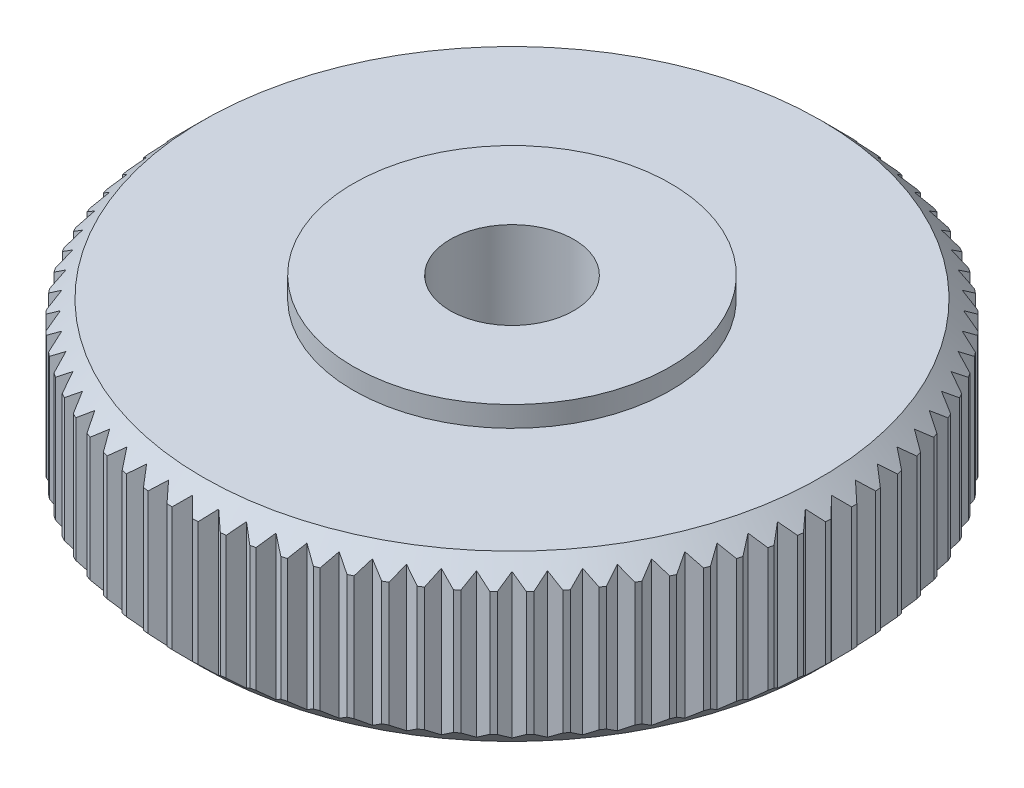
SolidWorks part; units mm, degrees
material "Chromowa stal nierdzewna"
ref_plane "Płaszczyzna przednia" through (0, 0, 0) normal (0, 0, 1) x (1, 0, 0)
ref_plane "Płaszczyzna górna" through (0, 0, 0) normal (0, 1, 0) x (1, 0, 0)
ref_plane "Płaszczyzna prawa" through (0, 0, 0) normal (1, 0, 0) x (0, 0, -1)
sketch "Szkic1" plane through (0, 0, 0) normal (0, 1, 0) x (1, 0, 0)
  circle A0 centre (0, 0) radius 8
  circle A1 centre (0, 0) radius 1.5
extrude "Dodanie-wyciągnięcie1" add sketch "Szkic1" along normal blind 4
chamfer "Sfazowanie1" distance 0.5 angle 45 2 edges at (0, 0, 8) (0, 4, 8)
sketch "Szkic2" plane through (0, 4, 0) normal (0, 1, 0) x (1, 0, 0)
  circle A0 centre (0, 0) radius 3.85
  circle A1 centre (0, 0) radius 1.5 construction
  circle A2 centre (0, 0) radius 1.5
extrude "Dodanie-wyciągnięcie2" add sketch "Szkic2" along normal blind 0.5
extrude "Dodanie-wyciągnięcie3" add sketch "Szkic2<2>" against normal blind 0.5 from surface starting at face at (0, 0, 7.5)
sketch "Szkic2<2>" plane through (0, 4, 0) normal (0, 1, 0) x (1, 0, 0) same geometry as "Szkic2"
sketch "Szkic3" plane through (0, 4, 0) normal (0, 1, 0) x (1, 0, 0)
  line L0 (8, 0) -> (7.75, 0) construction
  line L1 (7.996, -0.2524) -> (7.75, 0)
  line L2 (7.75, 0) -> (7.9962, 0.2476)
  line L3 (7.996, -0.2524) -> (8.6523, -0.2524)
  line L4 (8.6523, -0.2524) -> (8.6523, 0.2476)
  line L5 (7.9962, 0.2476) -> (8.6523, 0.2476)
  line L6 (7.9516, -0.8789) -> (7.7261, -0.6081)
  line L7 (7.7261, -0.6081) -> (7.9909, -0.3805)
  line L8 (7.9516, -0.8789) -> (8.6058, -0.9304)
  line L9 (8.6058, -0.9304) -> (8.645, -0.432)
  line L10 (7.9909, -0.3805) -> (8.645, -0.432)
  line L11 (7.9753, -0.6277) -> (7.7261, -0.6081) construction
  line L12 (7.8581, -1.5001) -> (7.6546, -1.2124)
  line L13 (7.6546, -1.2124) -> (7.9365, -1.0063)
  line L14 (7.8581, -1.5001) -> (8.5063, -1.6028)
  line L15 (8.5063, -1.6028) -> (8.5845, -1.1089)
  line L16 (7.9365, -1.0063) -> (8.5845, -1.1089)
  line L17 (7.9015, -1.2515) -> (7.6546, -1.2124) construction
  line L18 (7.7162, -2.112) -> (7.5359, -1.8092)
  line L19 (7.5359, -1.8092) -> (7.833, -1.6259)
  line L20 (7.7162, -2.112) -> (8.3543, -2.2652)
  line L21 (8.3543, -2.2652) -> (8.471, -1.779)
  line L22 (7.833, -1.6259) -> (8.471, -1.779)
  line L23 (7.779, -1.8676) -> (7.5359, -1.8092) construction
  line L24 (7.5267, -2.7109) -> (7.3707, -2.3949)
  line L25 (7.3707, -2.3949) -> (7.6813, -2.2354)
  line L26 (7.5267, -2.7109) -> (8.1508, -2.9137)
  line L27 (8.1508, -2.9137) -> (8.3053, -2.4382)
  line L28 (7.6813, -2.2354) -> (8.3053, -2.4382)
  line L29 (7.6085, -2.4721) -> (7.3707, -2.3949) construction
  line L30 (7.2908, -3.2931) -> (7.1601, -2.9658)
  line L31 (7.1601, -2.9658) -> (7.4823, -2.8312)
  line L32 (7.2908, -3.2931) -> (7.8971, -3.5442)
  line L33 (7.8971, -3.5442) -> (8.0884, -3.0823)
  line L34 (7.4823, -2.8312) -> (8.0884, -3.0823)
  line L35 (7.391, -3.0615) -> (7.1601, -2.9658) construction
  line L36 (7.0099, -3.855) -> (6.9053, -3.5184)
  line L37 (6.9053, -3.5184) -> (7.2371, -3.4095)
  line L38 (7.0099, -3.855) -> (7.5947, -4.1529)
  line L39 (7.5947, -4.1529) -> (7.8217, -3.7074)
  line L40 (7.2371, -3.4095) -> (7.8217, -3.7074)
  line L41 (7.1281, -3.6319) -> (6.9053, -3.5184) construction
  line L42 (6.6859, -4.3931) -> (6.608, -4.0494)
  line L43 (6.608, -4.0494) -> (6.9472, -3.9668)
  line L44 (6.6859, -4.3931) -> (7.2454, -4.736)
  line L45 (7.2454, -4.736) -> (7.5067, -4.3096)
  line L46 (6.9472, -3.9668) -> (7.5067, -4.3096)
  line L47 (6.8211, -4.18) -> (6.608, -4.0494) construction
  line L48 (6.3206, -4.9041) -> (6.2699, -4.5553)
  line L49 (6.2699, -4.5553) -> (6.6146, -4.4997)
  line L50 (6.3206, -4.9041) -> (6.8515, -5.2898)
  line L51 (6.8515, -5.2898) -> (7.1454, -4.8853)
  line L52 (6.6146, -4.4997) -> (7.1454, -4.8853)
  line L53 (6.4721, -4.7023) -> (6.2699, -4.5553) construction
  line L54 (5.9163, -5.3849) -> (5.8931, -5.0332)
  line L55 (5.8931, -5.0332) -> (6.2412, -5.0048)
  line L56 (5.9163, -5.3849) -> (6.4153, -5.8111)
  line L57 (6.4153, -5.8111) -> (6.7401, -5.4309)
  line L58 (6.2412, -5.0048) -> (6.7401, -5.4309)
  line L59 (6.0832, -5.1956) -> (5.8931, -5.0332) construction
  line L60 (5.4756, -5.8325) -> (5.4801, -5.4801)
  line L61 (5.4801, -5.4801) -> (5.8293, -5.479)
  line L62 (5.4756, -5.8325) -> (5.9396, -6.2965)
  line L63 (5.9396, -6.2965) -> (6.2932, -5.943)
  line L64 (5.8293, -5.479) -> (6.2932, -5.943)
  line L65 (5.6569, -5.6569) -> (5.4801, -5.4801) construction
  line L66 (5.0011, -6.2441) -> (5.0332, -5.8931)
  line L67 (5.0332, -5.8931) -> (5.3814, -5.9195)
  line L68 (5.0011, -6.2441) -> (5.4273, -6.7431)
  line L69 (5.4273, -6.7431) -> (5.8075, -6.4184)
  line L70 (5.3814, -5.9195) -> (5.8075, -6.4184)
  line L71 (5.1956, -6.0832) -> (5.0332, -5.8931) construction
  line L72 (4.4958, -6.6172) -> (4.5553, -6.2699)
  line L73 (4.5553, -6.2699) -> (4.9004, -6.3235)
  line L74 (4.4958, -6.6172) -> (4.8815, -7.1482)
  line L75 (4.8815, -7.1482) -> (5.286, -6.8543)
  line L76 (4.9004, -6.3235) -> (5.286, -6.8543)
  line L77 (4.7023, -6.4721) -> (4.5553, -6.2699) construction
  line L78 (3.9627, -6.9496) -> (4.0494, -6.608)
  line L79 (4.0494, -6.608) -> (4.3891, -6.6885)
  line L80 (3.9627, -6.9496) -> (4.3056, -7.5091)
  line L81 (4.3056, -7.5091) -> (4.732, -7.2479)
  line L82 (4.3891, -6.6885) -> (4.732, -7.2479)
  line L83 (4.18, -6.8211) -> (4.0494, -6.608) construction
  line L84 (3.4053, -7.2391) -> (3.5184, -6.9053)
  line L85 (3.5184, -6.9053) -> (3.8508, -7.0122)
  line L86 (3.4053, -7.2391) -> (3.7032, -7.8238)
  line L87 (3.7032, -7.8238) -> (4.1487, -7.5968)
  line L88 (3.8508, -7.0122) -> (4.1487, -7.5968)
  line L89 (3.6319, -7.1281) -> (3.5184, -6.9053) construction
  line L90 (2.8268, -7.4839) -> (2.9658, -7.1601)
  line L91 (2.9658, -7.1601) -> (3.2888, -7.2927)
  line L92 (2.8268, -7.4839) -> (3.0779, -8.0902)
  line L93 (3.0779, -8.0902) -> (3.5399, -7.8989)
  line L94 (3.2888, -7.2927) -> (3.5399, -7.8989)
  line L95 (3.0615, -7.391) -> (2.9658, -7.1601) construction
  line L96 (2.2309, -7.6826) -> (2.3949, -7.3707)
  line L97 (2.3949, -7.3707) -> (2.7065, -7.5283)
  line L98 (2.2309, -7.6826) -> (2.4337, -8.3068)
  line L99 (2.4337, -8.3068) -> (2.9092, -8.1523)
  line L100 (2.7065, -7.5283) -> (2.9092, -8.1523)
  line L101 (2.4721, -7.6085) -> (2.3949, -7.3707) construction
  line L102 (1.6213, -7.834) -> (1.8092, -7.5359)
  line L103 (1.8092, -7.5359) -> (2.1075, -7.7174)
  line L104 (1.6213, -7.834) -> (1.7745, -8.4721)
  line L105 (1.7745, -8.4721) -> (2.2606, -8.3554)
  line L106 (2.1075, -7.7174) -> (2.2606, -8.3554)
  line L107 (1.8676, -7.779) -> (1.8092, -7.5359) construction
  line L108 (1.0016, -7.9371) -> (1.2124, -7.6546)
  line L109 (1.2124, -7.6546) -> (1.4955, -7.859)
  line L110 (1.0016, -7.9371) -> (1.1043, -8.5852)
  line L111 (1.1043, -8.5852) -> (1.5981, -8.507)
  line L112 (1.4955, -7.859) -> (1.5981, -8.507)
  line L113 (1.2515, -7.9015) -> (1.2124, -7.6546) construction
  line L114 (0.3758, -7.9912) -> (0.6081, -7.7261)
  line L115 (0.6081, -7.7261) -> (0.8743, -7.9521)
  line L116 (0.3758, -7.9912) -> (0.4273, -8.6454)
  line L117 (0.4273, -8.6454) -> (0.9257, -8.6062)
  line L118 (0.8743, -7.9521) -> (0.9257, -8.6062)
  line L119 (0.6277, -7.9753) -> (0.6081, -7.7261) construction
  line L120 (-0.2524, -7.996) -> (0, -7.75)
  line L121 (0, -7.75) -> (0.2476, -7.9962)
  line L122 (-0.2524, -7.996) -> (-0.2524, -8.6523)
  line L123 (-0.2524, -8.6523) -> (0.2476, -8.6523)
  line L124 (0.2476, -7.9962) -> (0.2476, -8.6523)
  line L125 (0, -8) -> (0, -7.75) construction
  line L126 (-0.8789, -7.9516) -> (-0.6081, -7.7261)
  line L127 (-0.6081, -7.7261) -> (-0.3805, -7.9909)
  line L128 (-0.8789, -7.9516) -> (-0.9304, -8.6058)
  line L129 (-0.9304, -8.6058) -> (-0.432, -8.645)
  line L130 (-0.3805, -7.9909) -> (-0.432, -8.645)
  line L131 (-0.6277, -7.9753) -> (-0.6081, -7.7261) construction
  line L132 (-1.5001, -7.8581) -> (-1.2124, -7.6546)
  line L133 (-1.2124, -7.6546) -> (-1.0063, -7.9365)
  line L134 (-1.5001, -7.8581) -> (-1.6028, -8.5063)
  line L135 (-1.6028, -8.5063) -> (-1.1089, -8.5845)
  line L136 (-1.0063, -7.9365) -> (-1.1089, -8.5845)
  line L137 (-1.2515, -7.9015) -> (-1.2124, -7.6546) construction
  line L138 (-2.112, -7.7162) -> (-1.8092, -7.5359)
  line L139 (-1.8092, -7.5359) -> (-1.6259, -7.833)
  line L140 (-2.112, -7.7162) -> (-2.2652, -8.3543)
  line L141 (-2.2652, -8.3543) -> (-1.779, -8.471)
  line L142 (-1.6259, -7.833) -> (-1.779, -8.471)
  line L143 (-1.8676, -7.779) -> (-1.8092, -7.5359) construction
  line L144 (-2.7109, -7.5267) -> (-2.3949, -7.3707)
  line L145 (-2.3949, -7.3707) -> (-2.2354, -7.6813)
  line L146 (-2.7109, -7.5267) -> (-2.9137, -8.1508)
  line L147 (-2.9137, -8.1508) -> (-2.4382, -8.3053)
  line L148 (-2.2354, -7.6813) -> (-2.4382, -8.3053)
  line L149 (-2.4721, -7.6085) -> (-2.3949, -7.3707) construction
  line L150 (-3.2931, -7.2908) -> (-2.9658, -7.1601)
  line L151 (-2.9658, -7.1601) -> (-2.8312, -7.4823)
  line L152 (-3.2931, -7.2908) -> (-3.5442, -7.8971)
  line L153 (-3.5442, -7.8971) -> (-3.0823, -8.0884)
  line L154 (-2.8312, -7.4823) -> (-3.0823, -8.0884)
  line L155 (-3.0615, -7.391) -> (-2.9658, -7.1601) construction
  line L156 (-3.855, -7.0099) -> (-3.5184, -6.9053)
  line L157 (-3.5184, -6.9053) -> (-3.4095, -7.2371)
  line L158 (-3.855, -7.0099) -> (-4.1529, -7.5947)
  line L159 (-4.1529, -7.5947) -> (-3.7074, -7.8217)
  line L160 (-3.4095, -7.2371) -> (-3.7074, -7.8217)
  line L161 (-3.6319, -7.1281) -> (-3.5184, -6.9053) construction
  line L162 (-4.3931, -6.6859) -> (-4.0494, -6.608)
  line L163 (-4.0494, -6.608) -> (-3.9668, -6.9472)
  line L164 (-4.3931, -6.6859) -> (-4.736, -7.2454)
  line L165 (-4.736, -7.2454) -> (-4.3096, -7.5067)
  line L166 (-3.9668, -6.9472) -> (-4.3096, -7.5067)
  line L167 (-4.18, -6.8211) -> (-4.0494, -6.608) construction
  line L168 (-4.9041, -6.3206) -> (-4.5553, -6.2699)
  line L169 (-4.5553, -6.2699) -> (-4.4997, -6.6146)
  line L170 (-4.9041, -6.3206) -> (-5.2898, -6.8515)
  line L171 (-5.2898, -6.8515) -> (-4.8853, -7.1454)
  line L172 (-4.4997, -6.6146) -> (-4.8853, -7.1454)
  line L173 (-4.7023, -6.4721) -> (-4.5553, -6.2699) construction
  line L174 (-5.3849, -5.9163) -> (-5.0332, -5.8931)
  line L175 (-5.0332, -5.8931) -> (-5.0048, -6.2412)
  line L176 (-5.3849, -5.9163) -> (-5.8111, -6.4153)
  line L177 (-5.8111, -6.4153) -> (-5.4309, -6.7401)
  line L178 (-5.0048, -6.2412) -> (-5.4309, -6.7401)
  line L179 (-5.1956, -6.0832) -> (-5.0332, -5.8931) construction
  line L180 (-5.8325, -5.4756) -> (-5.4801, -5.4801)
  line L181 (-5.4801, -5.4801) -> (-5.479, -5.8293)
  line L182 (-5.8325, -5.4756) -> (-6.2965, -5.9396)
  line L183 (-6.2965, -5.9396) -> (-5.943, -6.2932)
  line L184 (-5.479, -5.8293) -> (-5.943, -6.2932)
  line L185 (-5.6569, -5.6569) -> (-5.4801, -5.4801) construction
  line L186 (-6.2441, -5.0011) -> (-5.8931, -5.0332)
  line L187 (-5.8931, -5.0332) -> (-5.9195, -5.3814)
  line L188 (-6.2441, -5.0011) -> (-6.7431, -5.4273)
  line L189 (-6.7431, -5.4273) -> (-6.4184, -5.8075)
  line L190 (-5.9195, -5.3814) -> (-6.4184, -5.8075)
  line L191 (-6.0832, -5.1956) -> (-5.8931, -5.0332) construction
  line L192 (-6.6172, -4.4958) -> (-6.2699, -4.5553)
  line L193 (-6.2699, -4.5553) -> (-6.3235, -4.9004)
  line L194 (-6.6172, -4.4958) -> (-7.1482, -4.8815)
  line L195 (-7.1482, -4.8815) -> (-6.8543, -5.286)
  line L196 (-6.3235, -4.9004) -> (-6.8543, -5.286)
  line L197 (-6.4721, -4.7023) -> (-6.2699, -4.5553) construction
  line L198 (-6.9496, -3.9627) -> (-6.608, -4.0494)
  line L199 (-6.608, -4.0494) -> (-6.6885, -4.3891)
  line L200 (-6.9496, -3.9627) -> (-7.5091, -4.3056)
  line L201 (-7.5091, -4.3056) -> (-7.2479, -4.732)
  line L202 (-6.6885, -4.3891) -> (-7.2479, -4.732)
  line L203 (-6.8211, -4.18) -> (-6.608, -4.0494) construction
  line L204 (-7.2391, -3.4053) -> (-6.9053, -3.5184)
  line L205 (-6.9053, -3.5184) -> (-7.0122, -3.8508)
  line L206 (-7.2391, -3.4053) -> (-7.8238, -3.7032)
  line L207 (-7.8238, -3.7032) -> (-7.5968, -4.1487)
  line L208 (-7.0122, -3.8508) -> (-7.5968, -4.1487)
  line L209 (-7.1281, -3.6319) -> (-6.9053, -3.5184) construction
  line L210 (-7.4839, -2.8268) -> (-7.1601, -2.9658)
  line L211 (-7.1601, -2.9658) -> (-7.2927, -3.2888)
  line L212 (-7.4839, -2.8268) -> (-8.0902, -3.0779)
  line L213 (-8.0902, -3.0779) -> (-7.8989, -3.5399)
  line L214 (-7.2927, -3.2888) -> (-7.8989, -3.5399)
  line L215 (-7.391, -3.0615) -> (-7.1601, -2.9658) construction
  line L216 (-7.6826, -2.2309) -> (-7.3707, -2.3949)
  line L217 (-7.3707, -2.3949) -> (-7.5283, -2.7065)
  line L218 (-7.6826, -2.2309) -> (-8.3068, -2.4337)
  line L219 (-8.3068, -2.4337) -> (-8.1523, -2.9092)
  line L220 (-7.5283, -2.7065) -> (-8.1523, -2.9092)
  line L221 (-7.6085, -2.4721) -> (-7.3707, -2.3949) construction
  line L222 (-7.834, -1.6213) -> (-7.5359, -1.8092)
  line L223 (-7.5359, -1.8092) -> (-7.7174, -2.1075)
  line L224 (-7.834, -1.6213) -> (-8.4721, -1.7745)
  line L225 (-8.4721, -1.7745) -> (-8.3554, -2.2606)
  line L226 (-7.7174, -2.1075) -> (-8.3554, -2.2606)
  line L227 (-7.779, -1.8676) -> (-7.5359, -1.8092) construction
  line L228 (-7.9371, -1.0016) -> (-7.6546, -1.2124)
  line L229 (-7.6546, -1.2124) -> (-7.859, -1.4955)
  line L230 (-7.9371, -1.0016) -> (-8.5852, -1.1043)
  line L231 (-8.5852, -1.1043) -> (-8.507, -1.5981)
  line L232 (-7.859, -1.4955) -> (-8.507, -1.5981)
  line L233 (-7.9015, -1.2515) -> (-7.6546, -1.2124) construction
  line L234 (-7.9912, -0.3758) -> (-7.7261, -0.6081)
  line L235 (-7.7261, -0.6081) -> (-7.9521, -0.8743)
  line L236 (-7.9912, -0.3758) -> (-8.6454, -0.4273)
  line L237 (-8.6454, -0.4273) -> (-8.6062, -0.9257)
  line L238 (-7.9521, -0.8743) -> (-8.6062, -0.9257)
  line L239 (-7.9753, -0.6277) -> (-7.7261, -0.6081) construction
  line L240 (-7.996, 0.2524) -> (-7.75, 0)
  line L241 (-7.75, 0) -> (-7.9962, -0.2476)
  line L242 (-7.996, 0.2524) -> (-8.6523, 0.2524)
  line L243 (-8.6523, 0.2524) -> (-8.6523, -0.2476)
  line L244 (-7.9962, -0.2476) -> (-8.6523, -0.2476)
  line L245 (-8, 0) -> (-7.75, 0) construction
  line L246 (-7.9516, 0.8789) -> (-7.7261, 0.6081)
  line L247 (-7.7261, 0.6081) -> (-7.9909, 0.3805)
  line L248 (-7.9516, 0.8789) -> (-8.6058, 0.9304)
  line L249 (-8.6058, 0.9304) -> (-8.645, 0.432)
  line L250 (-7.9909, 0.3805) -> (-8.645, 0.432)
  line L251 (-7.9753, 0.6277) -> (-7.7261, 0.6081) construction
  line L252 (-7.8581, 1.5001) -> (-7.6546, 1.2124)
  line L253 (-7.6546, 1.2124) -> (-7.9365, 1.0063)
  line L254 (-7.8581, 1.5001) -> (-8.5063, 1.6028)
  line L255 (-8.5063, 1.6028) -> (-8.5845, 1.1089)
  line L256 (-7.9365, 1.0063) -> (-8.5845, 1.1089)
  line L257 (-7.9015, 1.2515) -> (-7.6546, 1.2124) construction
  line L258 (-7.7162, 2.112) -> (-7.5359, 1.8092)
  line L259 (-7.5359, 1.8092) -> (-7.833, 1.6259)
  line L260 (-7.7162, 2.112) -> (-8.3543, 2.2652)
  line L261 (-8.3543, 2.2652) -> (-8.471, 1.779)
  line L262 (-7.833, 1.6259) -> (-8.471, 1.779)
  line L263 (-7.779, 1.8676) -> (-7.5359, 1.8092) construction
  line L264 (-7.5267, 2.7109) -> (-7.3707, 2.3949)
  line L265 (-7.3707, 2.3949) -> (-7.6813, 2.2354)
  line L266 (-7.5267, 2.7109) -> (-8.1508, 2.9137)
  line L267 (-8.1508, 2.9137) -> (-8.3053, 2.4382)
  line L268 (-7.6813, 2.2354) -> (-8.3053, 2.4382)
  line L269 (-7.6085, 2.4721) -> (-7.3707, 2.3949) construction
  line L270 (-7.2908, 3.2931) -> (-7.1601, 2.9658)
  line L271 (-7.1601, 2.9658) -> (-7.4823, 2.8312)
  line L272 (-7.2908, 3.2931) -> (-7.8971, 3.5442)
  line L273 (-7.8971, 3.5442) -> (-8.0884, 3.0823)
  line L274 (-7.4823, 2.8312) -> (-8.0884, 3.0823)
  line L275 (-7.391, 3.0615) -> (-7.1601, 2.9658) construction
  line L276 (-7.0099, 3.855) -> (-6.9053, 3.5184)
  line L277 (-6.9053, 3.5184) -> (-7.2371, 3.4095)
  line L278 (-7.0099, 3.855) -> (-7.5947, 4.1529)
  line L279 (-7.5947, 4.1529) -> (-7.8217, 3.7074)
  line L280 (-7.2371, 3.4095) -> (-7.8217, 3.7074)
  line L281 (-7.1281, 3.6319) -> (-6.9053, 3.5184) construction
  line L282 (-6.6859, 4.3931) -> (-6.608, 4.0494)
  line L283 (-6.608, 4.0494) -> (-6.9472, 3.9668)
  line L284 (-6.6859, 4.3931) -> (-7.2454, 4.736)
  line L285 (-7.2454, 4.736) -> (-7.5067, 4.3096)
  line L286 (-6.9472, 3.9668) -> (-7.5067, 4.3096)
  line L287 (-6.8211, 4.18) -> (-6.608, 4.0494) construction
  line L288 (-6.3206, 4.9041) -> (-6.2699, 4.5553)
  line L289 (-6.2699, 4.5553) -> (-6.6146, 4.4997)
  line L290 (-6.3206, 4.9041) -> (-6.8515, 5.2898)
  line L291 (-6.8515, 5.2898) -> (-7.1454, 4.8853)
  line L292 (-6.6146, 4.4997) -> (-7.1454, 4.8853)
  line L293 (-6.4721, 4.7023) -> (-6.2699, 4.5553) construction
  line L294 (-5.9163, 5.3849) -> (-5.8931, 5.0332)
  line L295 (-5.8931, 5.0332) -> (-6.2412, 5.0048)
  line L296 (-5.9163, 5.3849) -> (-6.4153, 5.8111)
  line L297 (-6.4153, 5.8111) -> (-6.7401, 5.4309)
  line L298 (-6.2412, 5.0048) -> (-6.7401, 5.4309)
  line L299 (-6.0832, 5.1956) -> (-5.8931, 5.0332) construction
  line L300 (-5.4756, 5.8325) -> (-5.4801, 5.4801)
  line L301 (-5.4801, 5.4801) -> (-5.8293, 5.479)
  line L302 (-5.4756, 5.8325) -> (-5.9396, 6.2965)
  line L303 (-5.9396, 6.2965) -> (-6.2932, 5.943)
  line L304 (-5.8293, 5.479) -> (-6.2932, 5.943)
  line L305 (-5.6569, 5.6569) -> (-5.4801, 5.4801) construction
  line L306 (-5.0011, 6.2441) -> (-5.0332, 5.8931)
  line L307 (-5.0332, 5.8931) -> (-5.3814, 5.9195)
  line L308 (-5.0011, 6.2441) -> (-5.4273, 6.7431)
  line L309 (-5.4273, 6.7431) -> (-5.8075, 6.4184)
  line L310 (-5.3814, 5.9195) -> (-5.8075, 6.4184)
  line L311 (-5.1956, 6.0832) -> (-5.0332, 5.8931) construction
  line L312 (-4.4958, 6.6172) -> (-4.5553, 6.2699)
  line L313 (-4.5553, 6.2699) -> (-4.9004, 6.3235)
  line L314 (-4.4958, 6.6172) -> (-4.8815, 7.1482)
  line L315 (-4.8815, 7.1482) -> (-5.286, 6.8543)
  line L316 (-4.9004, 6.3235) -> (-5.286, 6.8543)
  line L317 (-4.7023, 6.4721) -> (-4.5553, 6.2699) construction
  line L318 (-3.9627, 6.9496) -> (-4.0494, 6.608)
  line L319 (-4.0494, 6.608) -> (-4.3891, 6.6885)
  line L320 (-3.9627, 6.9496) -> (-4.3056, 7.5091)
  line L321 (-4.3056, 7.5091) -> (-4.732, 7.2479)
  line L322 (-4.3891, 6.6885) -> (-4.732, 7.2479)
  line L323 (-4.18, 6.8211) -> (-4.0494, 6.608) construction
  line L324 (-3.4053, 7.2391) -> (-3.5184, 6.9053)
  line L325 (-3.5184, 6.9053) -> (-3.8508, 7.0122)
  line L326 (-3.4053, 7.2391) -> (-3.7032, 7.8238)
  line L327 (-3.7032, 7.8238) -> (-4.1487, 7.5968)
  line L328 (-3.8508, 7.0122) -> (-4.1487, 7.5968)
  line L329 (-3.6319, 7.1281) -> (-3.5184, 6.9053) construction
  line L330 (-2.8268, 7.4839) -> (-2.9658, 7.1601)
  line L331 (-2.9658, 7.1601) -> (-3.2888, 7.2927)
  line L332 (-2.8268, 7.4839) -> (-3.0779, 8.0902)
  line L333 (-3.0779, 8.0902) -> (-3.5399, 7.8989)
  line L334 (-3.2888, 7.2927) -> (-3.5399, 7.8989)
  line L335 (-3.0615, 7.391) -> (-2.9658, 7.1601) construction
  line L336 (-2.2309, 7.6826) -> (-2.3949, 7.3707)
  line L337 (-2.3949, 7.3707) -> (-2.7065, 7.5283)
  line L338 (-2.2309, 7.6826) -> (-2.4337, 8.3068)
  line L339 (-2.4337, 8.3068) -> (-2.9092, 8.1523)
  line L340 (-2.7065, 7.5283) -> (-2.9092, 8.1523)
  line L341 (-2.4721, 7.6085) -> (-2.3949, 7.3707) construction
  line L342 (-1.6213, 7.834) -> (-1.8092, 7.5359)
  line L343 (-1.8092, 7.5359) -> (-2.1075, 7.7174)
  line L344 (-1.6213, 7.834) -> (-1.7745, 8.4721)
  line L345 (-1.7745, 8.4721) -> (-2.2606, 8.3554)
  line L346 (-2.1075, 7.7174) -> (-2.2606, 8.3554)
  line L347 (-1.8676, 7.779) -> (-1.8092, 7.5359) construction
  line L348 (-1.0016, 7.9371) -> (-1.2124, 7.6546)
  line L349 (-1.2124, 7.6546) -> (-1.4955, 7.859)
  line L350 (-1.0016, 7.9371) -> (-1.1043, 8.5852)
  line L351 (-1.1043, 8.5852) -> (-1.5981, 8.507)
  line L352 (-1.4955, 7.859) -> (-1.5981, 8.507)
  line L353 (-1.2515, 7.9015) -> (-1.2124, 7.6546) construction
  line L354 (-0.3758, 7.9912) -> (-0.6081, 7.7261)
  line L355 (-0.6081, 7.7261) -> (-0.8743, 7.9521)
  line L356 (-0.3758, 7.9912) -> (-0.4273, 8.6454)
  line L357 (-0.4273, 8.6454) -> (-0.9257, 8.6062)
  line L358 (-0.8743, 7.9521) -> (-0.9257, 8.6062)
  line L359 (-0.6277, 7.9753) -> (-0.6081, 7.7261) construction
  line L360 (0.2524, 7.996) -> (0, 7.75)
  line L361 (0, 7.75) -> (-0.2476, 7.9962)
  line L362 (0.2524, 7.996) -> (0.2524, 8.6523)
  line L363 (0.2524, 8.6523) -> (-0.2476, 8.6523)
  line L364 (-0.2476, 7.9962) -> (-0.2476, 8.6523)
  line L365 (0, 8) -> (0, 7.75) construction
  line L366 (0.8789, 7.9516) -> (0.6081, 7.7261)
  line L367 (0.6081, 7.7261) -> (0.3805, 7.9909)
  line L368 (0.8789, 7.9516) -> (0.9304, 8.6058)
  line L369 (0.9304, 8.6058) -> (0.432, 8.645)
  line L370 (0.3805, 7.9909) -> (0.432, 8.645)
  line L371 (0.6277, 7.9753) -> (0.6081, 7.7261) construction
  line L372 (1.5001, 7.8581) -> (1.2124, 7.6546)
  line L373 (1.2124, 7.6546) -> (1.0063, 7.9365)
  line L374 (1.5001, 7.8581) -> (1.6028, 8.5063)
  line L375 (1.6028, 8.5063) -> (1.1089, 8.5845)
  line L376 (1.0063, 7.9365) -> (1.1089, 8.5845)
  line L377 (1.2515, 7.9015) -> (1.2124, 7.6546) construction
  line L378 (2.112, 7.7162) -> (1.8092, 7.5359)
  line L379 (1.8092, 7.5359) -> (1.6259, 7.833)
  line L380 (2.112, 7.7162) -> (2.2652, 8.3543)
  line L381 (2.2652, 8.3543) -> (1.779, 8.471)
  line L382 (1.6259, 7.833) -> (1.779, 8.471)
  line L383 (1.8676, 7.779) -> (1.8092, 7.5359) construction
  line L384 (2.7109, 7.5267) -> (2.3949, 7.3707)
  line L385 (2.3949, 7.3707) -> (2.2354, 7.6813)
  line L386 (2.7109, 7.5267) -> (2.9137, 8.1508)
  line L387 (2.9137, 8.1508) -> (2.4382, 8.3053)
  line L388 (2.2354, 7.6813) -> (2.4382, 8.3053)
  line L389 (2.4721, 7.6085) -> (2.3949, 7.3707) construction
  line L390 (3.2931, 7.2908) -> (2.9658, 7.1601)
  line L391 (2.9658, 7.1601) -> (2.8312, 7.4823)
  line L392 (3.2931, 7.2908) -> (3.5442, 7.8971)
  line L393 (3.5442, 7.8971) -> (3.0823, 8.0884)
  line L394 (2.8312, 7.4823) -> (3.0823, 8.0884)
  line L395 (3.0615, 7.391) -> (2.9658, 7.1601) construction
  line L396 (3.855, 7.0099) -> (3.5184, 6.9053)
  line L397 (3.5184, 6.9053) -> (3.4095, 7.2371)
  line L398 (3.855, 7.0099) -> (4.1529, 7.5947)
  line L399 (4.1529, 7.5947) -> (3.7074, 7.8217)
  line L400 (3.4095, 7.2371) -> (3.7074, 7.8217)
  line L401 (3.6319, 7.1281) -> (3.5184, 6.9053) construction
  line L402 (4.3931, 6.6859) -> (4.0494, 6.608)
  line L403 (4.0494, 6.608) -> (3.9668, 6.9472)
  line L404 (4.3931, 6.6859) -> (4.736, 7.2454)
  line L405 (4.736, 7.2454) -> (4.3096, 7.5067)
  line L406 (3.9668, 6.9472) -> (4.3096, 7.5067)
  line L407 (4.18, 6.8211) -> (4.0494, 6.608) construction
  line L408 (4.9041, 6.3206) -> (4.5553, 6.2699)
  line L409 (4.5553, 6.2699) -> (4.4997, 6.6146)
  line L410 (4.9041, 6.3206) -> (5.2898, 6.8515)
  line L411 (5.2898, 6.8515) -> (4.8853, 7.1454)
  line L412 (4.4997, 6.6146) -> (4.8853, 7.1454)
  line L413 (4.7023, 6.4721) -> (4.5553, 6.2699) construction
  line L414 (5.3849, 5.9163) -> (5.0332, 5.8931)
  line L415 (5.0332, 5.8931) -> (5.0048, 6.2412)
  line L416 (5.3849, 5.9163) -> (5.8111, 6.4153)
  line L417 (5.8111, 6.4153) -> (5.4309, 6.7401)
  line L418 (5.0048, 6.2412) -> (5.4309, 6.7401)
  line L419 (5.1956, 6.0832) -> (5.0332, 5.8931) construction
  line L420 (5.8325, 5.4756) -> (5.4801, 5.4801)
  line L421 (5.4801, 5.4801) -> (5.479, 5.8293)
  line L422 (5.8325, 5.4756) -> (6.2965, 5.9396)
  line L423 (6.2965, 5.9396) -> (5.943, 6.2932)
  line L424 (5.479, 5.8293) -> (5.943, 6.2932)
  line L425 (5.6569, 5.6569) -> (5.4801, 5.4801) construction
  line L426 (6.2441, 5.0011) -> (5.8931, 5.0332)
  line L427 (5.8931, 5.0332) -> (5.9195, 5.3814)
  line L428 (6.2441, 5.0011) -> (6.7431, 5.4273)
  line L429 (6.7431, 5.4273) -> (6.4184, 5.8075)
  line L430 (5.9195, 5.3814) -> (6.4184, 5.8075)
  line L431 (6.0832, 5.1956) -> (5.8931, 5.0332) construction
  line L432 (6.6172, 4.4958) -> (6.2699, 4.5553)
  line L433 (6.2699, 4.5553) -> (6.3235, 4.9004)
  line L434 (6.6172, 4.4958) -> (7.1482, 4.8815)
  line L435 (7.1482, 4.8815) -> (6.8543, 5.286)
  line L436 (6.3235, 4.9004) -> (6.8543, 5.286)
  line L437 (6.4721, 4.7023) -> (6.2699, 4.5553) construction
  line L438 (6.9496, 3.9627) -> (6.608, 4.0494)
  line L439 (6.608, 4.0494) -> (6.6885, 4.3891)
  line L440 (6.9496, 3.9627) -> (7.5091, 4.3056)
  line L441 (7.5091, 4.3056) -> (7.2479, 4.732)
  line L442 (6.6885, 4.3891) -> (7.2479, 4.732)
  line L443 (6.8211, 4.18) -> (6.608, 4.0494) construction
  line L444 (7.2391, 3.4053) -> (6.9053, 3.5184)
  line L445 (6.9053, 3.5184) -> (7.0122, 3.8508)
  line L446 (7.2391, 3.4053) -> (7.8238, 3.7032)
  line L447 (7.8238, 3.7032) -> (7.5968, 4.1487)
  line L448 (7.0122, 3.8508) -> (7.5968, 4.1487)
  line L449 (7.1281, 3.6319) -> (6.9053, 3.5184) construction
  line L450 (7.4839, 2.8268) -> (7.1601, 2.9658)
  line L451 (7.1601, 2.9658) -> (7.2927, 3.2888)
  line L452 (7.4839, 2.8268) -> (8.0902, 3.0779)
  line L453 (8.0902, 3.0779) -> (7.8989, 3.5399)
  line L454 (7.2927, 3.2888) -> (7.8989, 3.5399)
  line L455 (7.391, 3.0615) -> (7.1601, 2.9658) construction
  line L456 (7.6826, 2.2309) -> (7.3707, 2.3949)
  line L457 (7.3707, 2.3949) -> (7.5283, 2.7065)
  line L458 (7.6826, 2.2309) -> (8.3068, 2.4337)
  line L459 (8.3068, 2.4337) -> (8.1523, 2.9092)
  line L460 (7.5283, 2.7065) -> (8.1523, 2.9092)
  line L461 (7.6085, 2.4721) -> (7.3707, 2.3949) construction
  line L462 (7.834, 1.6213) -> (7.5359, 1.8092)
  line L463 (7.5359, 1.8092) -> (7.7174, 2.1075)
  line L464 (7.834, 1.6213) -> (8.4721, 1.7745)
  line L465 (8.4721, 1.7745) -> (8.3554, 2.2606)
  line L466 (7.7174, 2.1075) -> (8.3554, 2.2606)
  line L467 (7.779, 1.8676) -> (7.5359, 1.8092) construction
  line L468 (7.9371, 1.0016) -> (7.6546, 1.2124)
  line L469 (7.6546, 1.2124) -> (7.859, 1.4955)
  line L470 (7.9371, 1.0016) -> (8.5852, 1.1043)
  line L471 (8.5852, 1.1043) -> (8.507, 1.5981)
  line L472 (7.859, 1.4955) -> (8.507, 1.5981)
  line L473 (7.9015, 1.2515) -> (7.6546, 1.2124) construction
  line L474 (7.9912, 0.3758) -> (7.7261, 0.6081)
  line L475 (7.7261, 0.6081) -> (7.9521, 0.8743)
  line L476 (7.9912, 0.3758) -> (8.6454, 0.4273)
  line L477 (8.6454, 0.4273) -> (8.6062, 0.9257)
  line L478 (7.9521, 0.8743) -> (8.6062, 0.9257)
  line L479 (7.9753, 0.6277) -> (7.7261, 0.6081) construction
  circle A0 centre (0, 0) radius 8 construction
  circle A1 centre (0, 0) radius 8 construction
  circle A2 centre (0, 0) radius 7.5 construction
  circle A3 centre (0, 0) radius 7.5 construction
  point P488 (0, 0)
  dimension "D1" = 0.5
  dimension "D2" = 0.25
  dimension "D3" = 80
extrude "Wytnij-wyciągnięcie2" cut sketch "Szkic3" against normal through all
